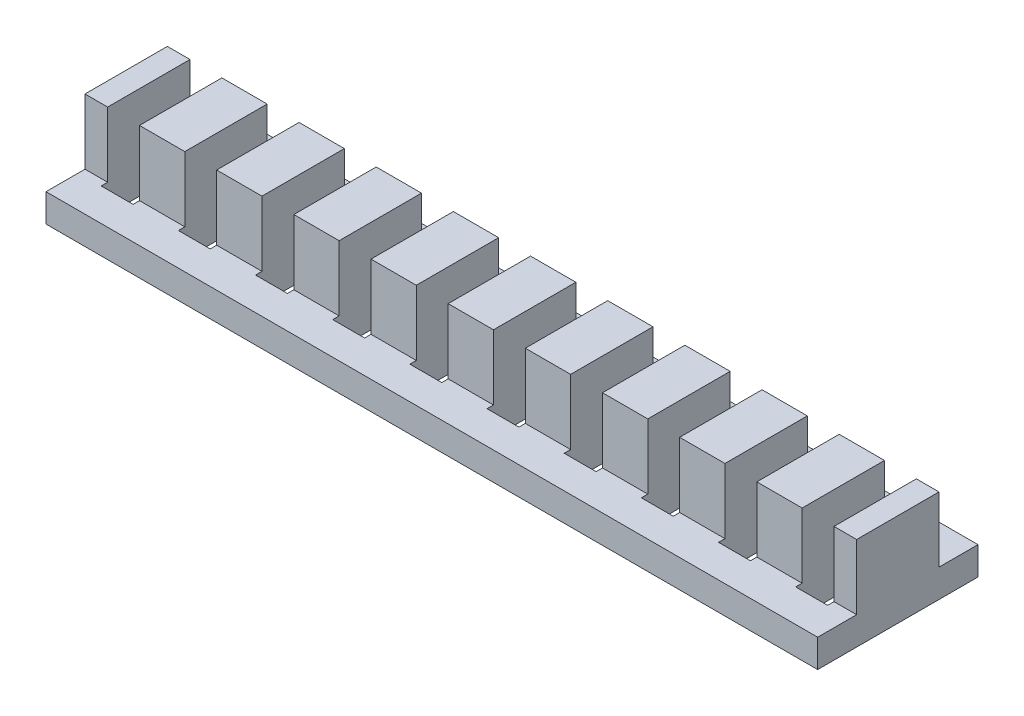
SolidWorks part; units mm, degrees
ref_plane "Front Plane" through (0, 0, 0) normal (0, 0, 1) x (1, 0, 0)
ref_plane "Top Plane" through (0, 0, 0) normal (0, 1, 0) x (1, 0, 0)
ref_plane "Right Plane" through (0, 0, 0) normal (1, 0, 0) x (0, 0, -1)
sketch "Sketch1" plane through (0, 0, 0) normal (0, 1, 0) x (1, 0, 0)
  line L1 (-38.5, -8) -> (38.5, -8)
  line L2 (-38.5, -8) -> (-38.5, 8)
  line L3 (-38.5, 8) -> (38.5, 8)
  line L4 (38.5, -8) -> (38.5, 8)
  line L5 (-38.5, -8) -> (38.5, 8) construction
  line L6 (-38.5, 8) -> (38.5, -8) construction
  point P0 (0, 0)
  dimension "D1" = 16
  dimension "D2" = 77
extrude "Boss-Extrude1" add sketch "Sketch1" along normal blind 2.8
sketch "Sketch2" plane through (0, 2.8, 0) normal (0, 1, 0) x (1, 0, 0)
  line L0 (-38.5, 8) -> (-38.5, -8) construction
  line L1 (-38.5, 4.11) -> (38.5, 4.11)
  line L2 (-38.5, 4.11) -> (-38.5, -4.11)
  line L3 (-38.5, -4.11) -> (38.5, -4.11)
  line L4 (38.5, 4.11) -> (38.5, -4.11)
  line L5 (38.5, -8) -> (38.5, 8) construction
  point P8 (-38.5, 0)
  point P9 (-38.5, 0)
  dimension "D1" = 8.22
extrude "Boss-Extrude2" add sketch "Sketch2" along normal blind 6.5
sketch "Sketch4" plane through (0, 0, 0) normal (0, -1, 0) x (1, 0, 0)
  line L0 (-28.54, 4.75) -> (-28.54, -4.75)
  line L1 (-36.24, 4.75) -> (-33.06, 4.75)
  line L2 (-36.24, 4.75) -> (-36.24, -4.75)
  line L3 (-36.24, -4.75) -> (-33.06, -4.75)
  line L4 (-33.06, 4.75) -> (-33.06, -4.75)
  line L5 (-28.54, 4.75) -> (-25.36, 4.75)
  line L6 (-34.65, 4.75) -> (-34.65, 8) construction
  line L7 (-38.5, 8) -> (38.5, 8) construction
  line L8 (-34.65, -4.75) -> (-34.65, -8) construction
  line L9 (38.5, -8) -> (-38.5, -8) construction
  line L10 (-25.36, 4.75) -> (-25.36, -4.75)
  line L11 (-28.54, -4.75) -> (-25.36, -4.75)
  line L12 (-20.84, 4.75) -> (-20.84, -4.75)
  line L13 (-20.84, 4.75) -> (-17.66, 4.75)
  line L14 (-17.66, 4.75) -> (-17.66, -4.75)
  line L15 (-20.84, -4.75) -> (-17.66, -4.75)
  line L16 (-13.14, 4.75) -> (-13.14, -4.75)
  line L17 (-13.14, 4.75) -> (-9.96, 4.75)
  line L18 (-9.96, 4.75) -> (-9.96, -4.75)
  line L19 (-13.14, -4.75) -> (-9.96, -4.75)
  line L20 (-5.44, 4.75) -> (-5.44, -4.75)
  line L21 (-5.44, 4.75) -> (-2.26, 4.75)
  line L22 (-2.26, 4.75) -> (-2.26, -4.75)
  line L23 (-5.44, -4.75) -> (-2.26, -4.75)
  line L24 (2.26, 4.75) -> (2.26, -4.75)
  line L25 (2.26, 4.75) -> (5.44, 4.75)
  line L26 (5.44, 4.75) -> (5.44, -4.75)
  line L27 (2.26, -4.75) -> (5.44, -4.75)
  line L28 (9.96, 4.75) -> (9.96, -4.75)
  line L29 (9.96, 4.75) -> (13.14, 4.75)
  line L30 (13.14, 4.75) -> (13.14, -4.75)
  line L31 (9.96, -4.75) -> (13.14, -4.75)
  line L32 (17.66, 4.75) -> (17.66, -4.75)
  line L33 (17.66, 4.75) -> (20.84, 4.75)
  line L34 (20.84, 4.75) -> (20.84, -4.75)
  line L35 (17.66, -4.75) -> (20.84, -4.75)
  line L36 (25.36, 4.75) -> (25.36, -4.75)
  line L37 (25.36, 4.75) -> (28.54, 4.75)
  line L38 (28.54, 4.75) -> (28.54, -4.75)
  line L39 (25.36, -4.75) -> (28.54, -4.75)
  line L40 (33.06, 4.75) -> (33.06, -4.75)
  line L41 (33.06, 4.75) -> (36.24, 4.75)
  line L42 (36.24, 4.75) -> (36.24, -4.75)
  line L43 (33.06, -4.75) -> (36.24, -4.75)
  line L44 (-2.26, 0) -> (2.26, 0) construction
  line L45 (-26.95, 4.75) -> (-26.95, 8) construction
  point P50 (0, 0)
  dimension "D1" = 3.18
  dimension "D2" = 9.5
  dimension "D3" = 10
  dimension "D5" = 7.7
extrude "Cut-Extrude1" cut sketch "Sketch4" against normal through all
equation "\"Width\"= 16"
equation "\"D1@Sketch1\"=\"Width\""
equation "\"D2@Sketch1\"=\"Length\""
equation "\"pinWidth\"= 8.22"
equation "\"D1@Sketch2\"=\"pinWidth\""
equation "\"pinCount\" = 10"
equation "\"interspace\"= 4.52"
equation "\"pinLength\"= 3.18"
equation "\"Length\"= ( \"pinLength\" + \"interspace\" ) * \"pinCount\""
equation "\"mLength\" = \"Width\""
